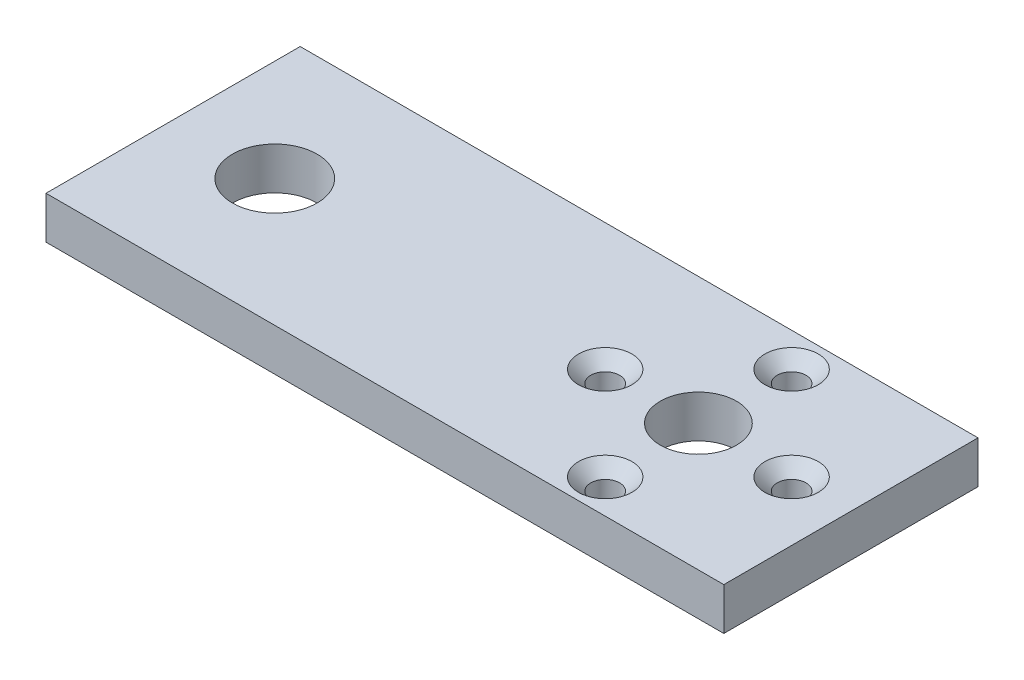
SolidWorks part; units mm, degrees
ref_plane "Front Plane" through (0, 0, 0) normal (0, 0, 1) x (1, 0, 0)
ref_plane "Top Plane" through (0, 0, 0) normal (0, 1, 0) x (1, 0, 0)
ref_plane "Right Plane" through (0, 0, 0) normal (1, 0, 0) x (0, 0, -1)
sketch "Sketch1" plane through (0, 0, 0) normal (0, 1, 0) x (1, 0, 0)
  line L0 (0, 46.1538) -> (0, -56.7033) construction
  line L1 (-129.2308, 0) -> (126.9231, 0) construction
  line L3 (-40, -15) -> (40, -15)
  line L4 (-40, -15) -> (-40, 15)
  line L5 (-40, 15) -> (40, 15)
  line L6 (40, -15) -> (40, 15)
  line L7 (-40, -15) -> (40, 15) construction
  line L8 (-40, 15) -> (40, -15) construction
  circle A0 centre (22, 0) radius 4.5
  circle A1 centre (-28, 0) radius 5
  point P5 (0, 0)
  dimension "D3" = 18
  dimension "D5" = 10
  dimension "D1" = 80
  dimension "D2" = 30
  dimension "D4" = 50
extrude "Boss-Extrude1" add sketch "Sketch1" along normal blind 5 contours L5 L6 L3 L4 | A0 | A1
sketch "Sketch2" plane through (0, 5, 0) normal (0, 1, 0) x (1, 0, 0)
  line L0 (26.5, 0) -> (17.5, 0) construction
  line L1 (22, 4.5) -> (22, -4.5) construction
  circle A0 centre (22, 0) radius 4.5 construction
  point P7 (11, 0)
  dimension "D1" = 11
hole_wizard "CSK for M3 Countersunk Flat Head Screw1" positions "Sketch3" profile "Sketch4" countersink size "M3" standard "ISO" end condition up to next
sketch "Sketch3" plane through (0, 5, 0) normal (0, 1, 0) x (1, 0, 0)
  point P0 (11, 0)
sketch "Sketch4" plane through (11, 5, 0) normal (1, 0, 0) x (0, 0, 1)
  line L0 (0, 0) -> (0, 5.001)
  line L1 (0, 5.001) -> (1.7, 5.001)
  line L2 (1.7, 5.001) -> (1.7, 1.45)
  line L3 (1.7, 1.45) -> (3.15, 0)
  line L5 (3.15, 0) -> (0, 0)
  line L6 (-1.7, 1.45) -> (-3.15, 0) construction
  line L11 (0, -6.35) -> (0, 107.95) construction
  dimension "Thru Hole Dia." = 3.4
  dimension "Thru Hole Depth" = 5.001
  dimension "Near C'Sink Dia." = 6.3
  dimension "Near C'Sink Angle" = 90
ref_axis "Axis1" through (22, 5, 0) along (0, -1, 0)
pattern_circular "CirPattern1" count 4 every 90 about axis through (22, 5, 0) along (0, -1, 0) of "CSK for M3 Countersunk Flat Head Screw1"
